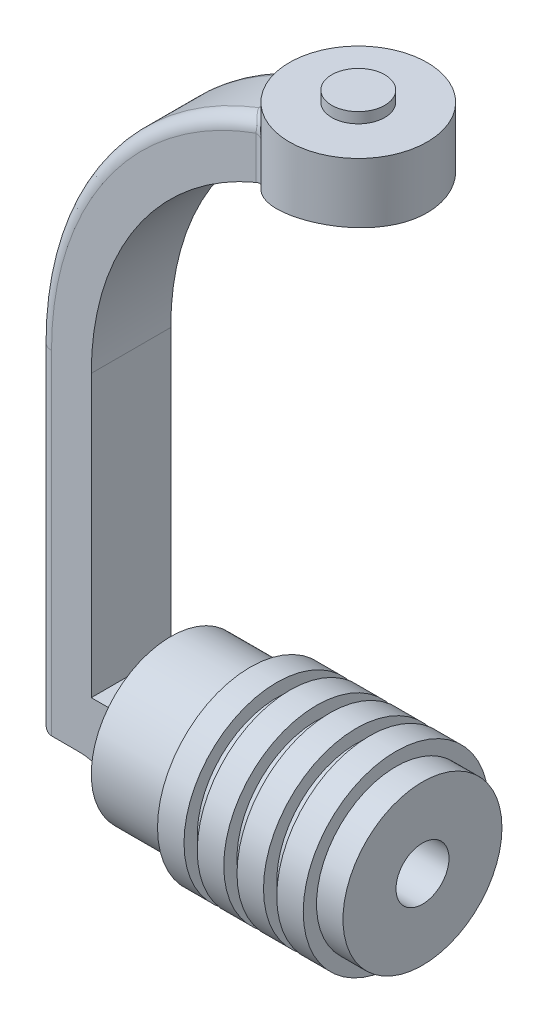
SolidWorks part; units mm, degrees
ref_plane "Ön Düzlem" through (0, 0, 0) normal (0, 0, 1) x (1, 0, 0)
ref_plane "Üst Düzlem" through (0, 0, 0) normal (0, 1, 0) x (1, 0, 0)
ref_plane "Sağ Düzlem" through (0, 0, 0) normal (1, 0, 0) x (0, 0, -1)
sketch "Sketch1" plane through (0, 0, 0) normal (0, 0, 1) x (1, 0, 0)
  line L0 (0, 0) -> (-110, 0) construction
  line L1 (-110, 0) -> (-110, -20)
  line L2 (-110, -20) -> (-90, -20)
  line L3 (-90, -20) -> (-90, -40)
  line L4 (-90, -40) -> (-130, -40)
  line L5 (-130, -40) -> (-130, 86)
  line L6 (-110, 0) -> (-110, 86)
  line L7 (-130, 86) -> (-110, 86) construction
  line L8 (0, 0) -> (0, 190) construction
  line L9 (-43.891, 181.0606) -> (-43.891, 202.1573)
  line L10 (0, 190) -> (-26, 190) construction
  arc A0 (-110, 86) -> (-43.891, 181.0606) centre (-8.6, 86) cw
  arc A1 (-130, 86) -> (-43.891, 202.1573) centre (-8.6, 86) cw
  point P12 (0, 0)
  point P14 (0, 0)
  point P16 (-43.891, 202.1247)
  dimension "D7" = 101.4
  dimension "D1" = 20
  dimension "D2" = 40
  dimension "D3" = 20
  dimension "D4" = 40
  dimension "D5" = 110
  dimension "D6" = 86
  dimension "D8" = 190
  dimension "D10" = 26
  dimension "D11" = 20
extrude "Boss-Extrude1" add sketch "Sketch1" along normal blind 30
sketch "Sketch2" plane through (-90, 0, 0) normal (1, 0, 0) x (0, 0, -1)
  line L0 (-30, -30) -> (0, -30) construction
  line L1 (-30, -40) -> (-30, -20) construction
  line L2 (0, -40) -> (0, -20) construction
  circle A0 centre (-15, -30) radius 30
  dimension "D1" = 60
extrude "Boss-Extrude2" add sketch "Sketch2" along normal blind 90 and the other way blind 5
sketch "Sketch3" plane through (0, 0, 0) normal (1, 0, 0) x (0, 0, -1)
  circle A0 centre (-15, -30) radius 35
  dimension "D1" = 70
extrude "Boss-Extrude3" add sketch "Sketch3" against normal blind 10 from offset 10 offset against normal yes
pattern_linear "LPattern1" count 4 spacing 15 along (-1, 0, 0) of "Boss-Extrude3"
sketch "Sketch4" plane through (0, 0, 0) normal (1, 0, 0) x (0, 0, -1)
  circle A0 centre (-15, -30) radius 10
  dimension "D1" = 20
extrude "Cut-Extrude1" cut sketch "Sketch4" against normal blind 20
ref_plane "Plane1" through (0, 0, 0) normal (0, 1, 0) x (1, 0, 0)
ref_plane "Plane2" through (0, 190, 0) normal (0, 1, 0) x (1, 0, 0)
sketch "Sketch5" plane through (0, 190, 0) normal (0, 1, 0) x (1, 0, 0)
  line L0 (-43.891, -15) -> (-4.561, -15) construction
  line L1 (-43.891, -30) -> (-43.891, 0) construction
  circle A0 centre (-24.226, -15) radius 26
  dimension "D2" = 52
  dimension "D1" = 39.33
extrude "Boss-Extrude4" add sketch "Sketch5" along normal blind 20 and the other way up to surface other way up to face at (-84.3967, 138.7122, 15)
sketch "Sketch7" plane through (0, 210, 0) normal (0, 1, 0) x (1, 0, 0)
  circle A0 centre (-24.226, -15) radius 10
  dimension "D1" = 20
extrude "Boss-Extrude6" add sketch "Sketch7" along normal blind 4
fillet "Fillet1" radius 20 1 edges at (-95, -40, 15)
fillet "Fillet4" radius 5 8 edges at (-45.4627, 191.0651, 0) (-45.4627, 191.0651, 30) (-130, -40, 15) (-130, 23, 0) (-130, 23, 30) (-106.613, 157.6339, 0) (-106.613, 157.6339, 30) (-50.0234, 200.1143, 11.7605)
